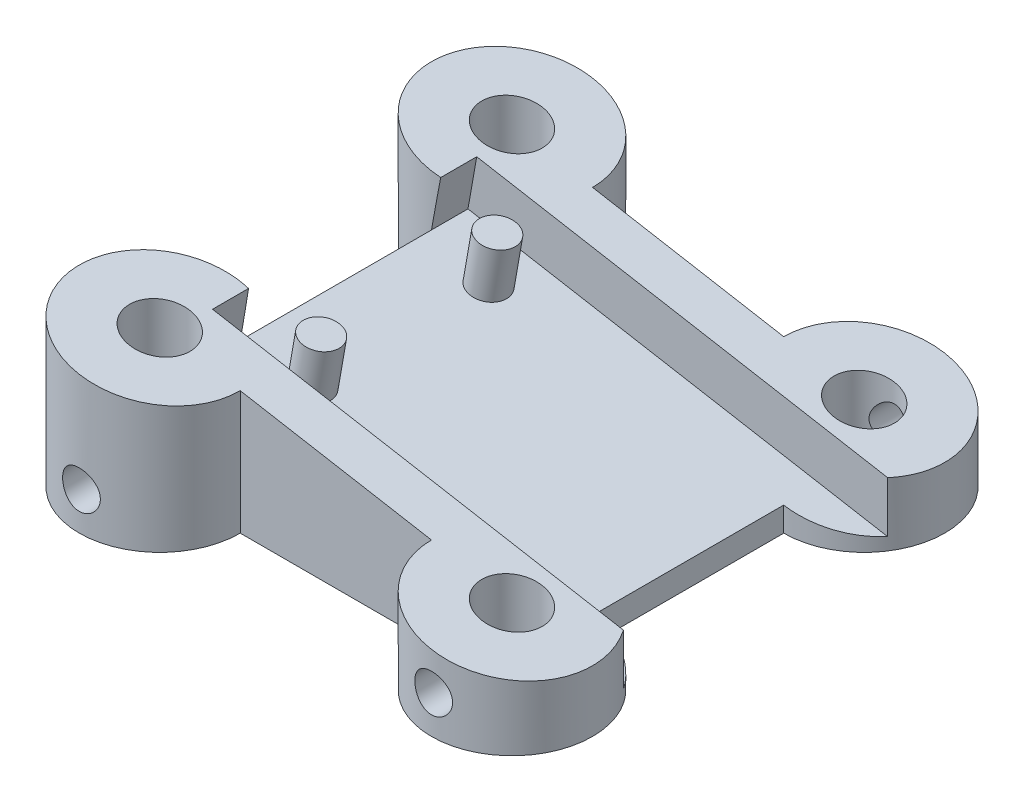
SolidWorks part; units mm, degrees
ref_plane "Front Plane" through (0, 0, 0) normal (0, 0, 1) x (1, 0, 0)
ref_plane "Top Plane" through (0, 0, 0) normal (0, 1, 0) x (1, 0, 0)
ref_plane "Right Plane" through (0, 0, 0) normal (1, 0, 0) x (0, 0, -1)
sketch "Sketch1" plane through (0, 0, 0) normal (0, 1, 0) x (1, 0, 0)
  line L0 (14, 28) -> (14, 0) construction
  line L1 (0, 0) -> (28, 0)
  line L2 (0, 0) -> (0, 28)
  line L3 (0, 28) -> (28, 28)
  line L4 (28, 0) -> (28, 28)
  line L5 (0, 14) -> (28, 14) construction
  point P9 (14, 14)
  dimension "D1" = 28
extrude "Boss-Extrude1" add sketch "Sketch1" along normal blind 10.9372
sketch "Sketch2" plane through (0, 0, 0) normal (0, 0, 1) x (1, 0, 0)
  line L0 (0, 10.9372) -> (28, 6)
  line L1 (0, 10.9372) -> (28, 10.9372) construction
  line L2 (28, 10.9372) -> (28, 0) construction
  line L3 (0, 10.9372) -> (28, 10.9372)
  line L4 (28, 10.9372) -> (28, 6)
  dimension "D2" = 6
  dimension "D3" = 10
extrude "Cut-Extrude1" cut sketch "Sketch2" against normal through all
sketch "Sketch3" plane through (1.8704, 10.6074, 0) normal (0.1736, 0.9848, 0) x (0.9848, -0.1736, 0)
  line L0 (-1.8992, 28) -> (-1.8992, 0) construction
  line L1 (-1.8992, 3.5) -> (48.1008, 3.5)
  line L2 (-1.8992, 3.5) -> (-1.8992, 24.5)
  line L3 (-1.8992, 24.5) -> (48.1008, 24.5)
  line L4 (48.1008, 3.5) -> (48.1008, 24.5)
  point P9 (-1.8992, 14)
  point P10 (-1.8992, 14)
  dimension "D1" = 21
  dimension "D2" = 50
extrude "Cut-Extrude2" cut sketch "Sketch3" against normal blind 4
ref_plane "Plane1" through (0, 10.9372, 0) normal (0, 1, 0) x (1, 0, 0)
sketch "Sketch11" plane through (1.1758, 6.6681, 0) normal (0.1736, 0.9848, 0) x (0.9848, -0.1736, 0)
  line L0 (27.238, 24.5) -> (-1.1939, 24.5) construction
  line L1 (27.238, 24.5) -> (27.238, 3.5) construction
  line L2 (-1.1939, 3.5) -> (27.238, 3.5) construction
  line L3 (27.238, 24.5) -> (-1.1939, 24.5) construction
  line L4 (27.238, 24.5) -> (27.238, 3.5) construction
  line L5 (-1.1939, 3.5) -> (27.238, 3.5) construction
  line L6 (13.0221, 3) -> (13.0221, 50003) construction
  line L7 (24.633, 14) -> (-49975.367, 14) construction
  circle A2 centre (4.0221, 21) radius 1.45
  circle A3 centre (4.0221, 7) radius 1.45
  point P6 (13.0221, 3.5)
  point P9 (27.238, 14)
  dimension "D4" = 2.9
  dimension "D5" = 9
  dimension "D6" = 7
extrude "Boss-Extrude2" add sketch "Sketch11" along normal blind 4
sketch "Sketch12" plane through (0, 10.9372, 0) normal (0, 1, 0) x (1, 0, 0)
  line L0 (0, 3.5) -> (0, 24.5) construction
  line L1 (0, 3.5) -> (28, 3.5) construction
  line L2 (0, 3.5) -> (0, 24.5) construction
  line L3 (0, 3.5) -> (28, 3.5) construction
  line L4 (0, 14) -> (50000, 14) construction
  line L5 (14, 4) -> (14, 50004) construction
  circle A0 centre (14, 14) radius 7
  point P7 (0, 14)
  point P10 (14, 3.5)
  dimension "D1" = 14
sketch "Sketch13" plane through (0, 0, 0) normal (0, -1, 0) x (1, 0, 0)
  line L0 (0, 0) -> (28, 0) construction
  line L1 (28, 0) -> (28, -28) construction
  line L2 (28, -28) -> (0, -28) construction
  line L3 (0, -28) -> (0, 0) construction
  line L4 (0, 0) -> (28, 0) construction
  line L5 (28, 0) -> (28, -28) construction
  line L6 (28, -28) -> (0, -28) construction
  line L7 (0, -28) -> (0, 0) construction
  line L8 (0, -14) -> (28, -14) construction
  line L9 (14, -28) -> (14, 0) construction
  circle A0 centre (0, 0) radius 2.4
  circle A1 centre (28, 0) radius 2.4
  circle A2 centre (28, -28) radius 2.4
  circle A3 centre (0, -28) radius 2.4
  dimension "D1" = 4.8
  dimension "D2" = 2
  dimension "D3" = 2
extrude "Cut-Extrude5" cut sketch "Sketch13" against normal through all
sketch "Sketch14" plane through (0, 0, 0) normal (0, -1, 0) x (1, 0, 0)
  line L0 (28, -3.5) -> (28, -2.4) construction
  line L1 (2.4, -28) -> (25.6, -28) construction
  line L2 (0, -3.5) -> (0, -24.5) construction
  circle A0 centre (0, 0) radius 2.4 construction
  circle A1 centre (0, 0) radius 2.4 construction
  circle A2 centre (0, 0) radius 6.4
  circle A3 centre (0, 0) radius 2.4
  circle A4 centre (28, 0) radius 2.4
  circle A5 centre (28, 0) radius 6.4
  circle A6 centre (28, -28) radius 2.4
  circle A7 centre (28, -28) radius 6.4
  circle A8 centre (0, -28) radius 2.4
  circle A9 centre (0, -28) radius 6.4
  dimension "D1" = 4
  dimension "D4" = 4.8
  dimension "D2" = 2
  dimension "D3" = 2
extrude "Boss-Extrude3" add sketch "Sketch14" against normal up to surface (10.9372 mm away) up to face at (14, 8.4686, -25.8676)
sketch "Sketch15" plane through (0, 0, -28) normal (0, 0, -1) x (-1, 0, 0)
  line L0 (-21.6, 0) -> (-6.4, 0) construction
  line L1 (-21.9, 0) -> (-0.9, 0) construction
  line L4 (-14, 8.4686) -> (-14, 0) construction
  line L5 (-6.4, 9.8087) -> (-21.6, 7.1285) construction
  circle A0 centre (-28, 3) radius 1.5
  circle A1 centre (0, 3) radius 1.5
  point P4 (-28, 0)
  dimension "D1" = 3
  dimension "D2" = 3
extrude "Cut-Extrude6" cut sketch "Sketch15" along normal through all
sketch "Sketch16" plane through (0, 0, 0) normal (0, 0, 1) x (1, 0, 0)
  circle A0 centre (0, 3) radius 1.5 construction
  circle A1 centre (28, 3) radius 1.5 construction
  circle A2 centre (0, 3) radius 1.5
  circle A3 centre (28, 3) radius 1.5
extrude "Cut-Extrude7" cut sketch "Sketch16" along normal through all
sketch "Sketch18" plane through (1.8704, 10.6074, 0) normal (0.1736, 0.9848, 0) x (0.9848, -0.1736, 0)
  line L5 (-1.8992, 3.5) -> (25.6754, 3.5) construction
  line L8 (3.5416, 3.5) -> (21.0919, 3.5) construction
  line L9 (3.5416, 3.5) -> (21.0919, 3.5) construction
  line L22 (4.2469, 24.5) -> (-1.1939, 24.5)
  line L37 (6.0919, 3.5) -> (36.0919, 3.5)
  line L38 (6.0919, 3.5) -> (6.0919, 24.5)
  line L39 (6.0919, 24.5) -> (36.0919, 24.5)
  line L40 (36.0919, 3.5) -> (36.0919, 24.5)
  line L42 (-1.1939, 24.5) -> (-1.1939, 21.6)
  line L46 (-1.1939, 6.4) -> (-1.1939, 3.5)
  line L47 (-1.1939, 3.5) -> (4.2469, 3.5)
  line L49 (3.5416, 24.5) -> (21.0919, 24.5) construction
  ellipse E1 centre (-1.1939, 28) end of major axis (5.3048, 28) minor radius 6.4 (-1.1939, 21.6) -> (4.2469, 24.5) ccw construction
  ellipse E2 centre (-1.1939, 28) end of major axis (5.3048, 28) minor radius 6.4 (-1.1939, 21.6) -> (4.2469, 24.5) ccw
  ellipse E3 centre (-1.1939, 0) end of major axis (5.3048, 0) minor radius 6.4 (4.2469, 3.5) -> (-1.1939, 6.4) ccw construction
  ellipse E4 centre (-1.1939, 0) end of major axis (5.3048, 0) minor radius 6.4 (4.2469, 3.5) -> (-1.1939, 6.4) ccw
  point P7 (21.0919, 3.5)
  dimension "D1" = 30
extrude "Cut-Extrude8" cut sketch "Sketch18" against normal up to surface (4 mm away) up to face at (6.5647, 5.7179, -21)
equation "\"TrackLength\"= 150"
equation "\"MarbleWidth\"= 13"
equation "\"MarbleTrackWidth\"= \"MarbleWidth\" - 1"
equation "\"TrackWidth\"= \"MarbleTrackWidth\" + ( 2 * 4 )"
equation "\"MarbleTrackLength\"= \"TrackLength\" - ( 2 * 8 )"
equation "\"MountWidth\"= \"TrackWidth\" + 8"
equation "\"D1@Sketch1\"=\"MountWidth\""
equation "\"D1@Boss-Extrude1\"=\"RampHeight\""
equation "\"RampDepth\"=6"
equation "\"RampAngle\"= 10"
equation "\"RampHeight\"= ( \"MountWidth\" * tan ( \"RampAngle\" ) ) + \"RampDepth\""
equation "\"D1@Sketch3\"=\"TrackWidth\" + 1"
equation "\"MountWidth\"= \"TrackWidth\" + 10"
equation "\"MountLength\"=66.6651"
